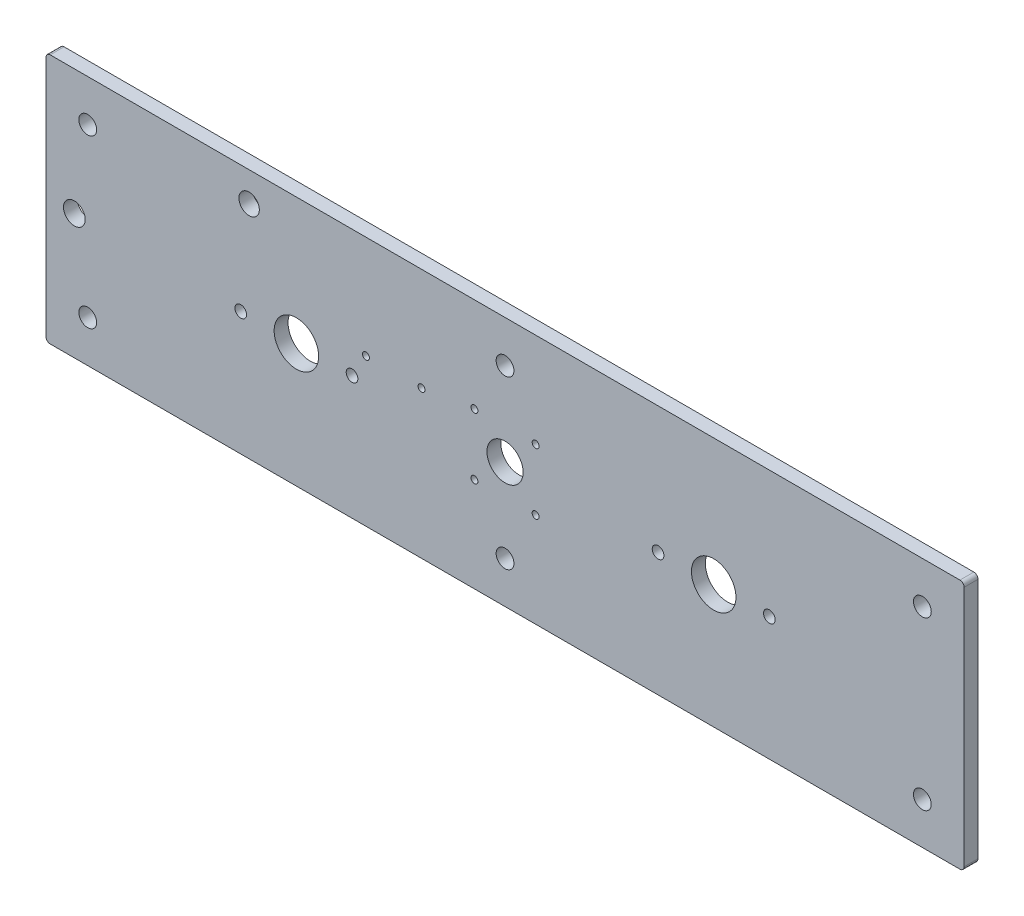
SolidWorks part; units mm, degrees
ref_plane "Front Plane" through (0, 0, 0) normal (0, 0, 1) x (1, 0, 0)
ref_plane "Top Plane" through (0, 0, 0) normal (0, 1, 0) x (1, 0, 0)
ref_plane "Right Plane" through (0, 0, 0) normal (1, 0, 0) x (0, 0, -1)
sketch "Sketch1" plane through (0, 0, 0) normal (0, 0, 1) x (1, 0, 0)
  line L1 (-165, -45) -> (165, -45)
  line L2 (-165, -45) -> (-165, 45)
  line L3 (-165, 45) -> (165, 45)
  line L4 (165, -45) -> (165, 45)
  line L5 (-165, -45) -> (165, 45) construction
  line L6 (-165, 45) -> (165, -45) construction
  point P0 (0, 0)
  dimension "D1" = 330
  dimension "D2" = 90
extrude "Boss-Extrude1" add sketch "Sketch1" along normal mid plane 5
hole_wizard "M6 Clearance Hole1" positions "Sketch6" profile "Sketch5" hole size "M6" standard "ANSI Metric"
sketch "Sketch6" plane through (0, 0, 2.5) normal (0, 0, 1) x (1, 0, 0)
  line L0 (-999.1588, 30) -> (49000.8412, 30) construction
  line L1 (-996.5045, -30) -> (49003.4955, -30) construction
  line L2 (-150, -995.3212) -> (-150, 49004.6788) construction
  line L3 (0, -1000) -> (0, 49000) construction
  line L4 (150, -1006.2702) -> (150, 48993.7298) construction
  line L5 (-165, 45) -> (-165, -45) construction
  line L6 (165, -45) -> (165, 45) construction
  line L7 (165, 45) -> (-165, 45) construction
  line L8 (-165, -45) -> (165, -45) construction
  point P27 (-150, 30)
  point P29 (-150, -30)
  point P31 (0, 30)
  point P33 (0, -30)
  point P35 (150, -30)
  point P37 (150, 30)
  dimension "D1" = 15
  dimension "D2" = 15
  dimension "D3" = 15
  dimension "D4" = 15
sketch "Sketch5" plane through (-150, 30, 2.5) normal (1, 0, 0) x (0, -1, 0)
  line L0 (0, 0) -> (0, 11.9228)
  line L1 (0, 11.9228) -> (3.2, 10)
  line L2 (3.2, 10) -> (3.2, 0)
  line L5 (3.2, 0) -> (0, 0)
  line L10 (0, 11.9228) -> (-3.2, 10) construction
  line L11 (0, -6.35) -> (0, 107.95) construction
  dimension "Hole Dia." = 6.4
  dimension "Hole Depth" = 10
  dimension "Drill Angle" = 118
sketch "Sketch3" plane through (0, 0, 2.5) normal (0, 0, 1) x (1, 0, 0)
  line L0 (-165, -0.6) -> (165, -0.6) construction
  circle A0 centre (-75, -0.6) radius 8
  dimension "D1" = 16
  dimension "D7" = 75
  dimension "D3" = 0.6
extrude "Cut-Extrude2" cut sketch "Sketch3" against normal through all
hole_wizard "M5x0.8 Tapped Hole1" positions "Sketch8" profile "Sketch7" tap size "M5x0.8" standard "ANSI Metric" end condition through all
sketch "Sketch8" plane through (0, 0, 2.5) normal (0, 0, 1) x (1, 0, 0)
  line L0 (-1080, -0.6) -> (48920, -0.6) construction
  circle A0 centre (-75, -0.6) radius 8 construction
  point P6 (-95, -0.6)
  point P8 (-55, -0.6)
  dimension "D1" = 20
  dimension "D2" = 20
sketch "Sketch7" plane through (-95, -0.6, 2.5) normal (1, 0, 0) x (0, -1, 0)
  line L0 (0, 0) -> (0, 5)
  line L1 (0, 5) -> (2.1, 5)
  line L2 (2.1, 5) -> (2.1, 0)
  line L5 (2.1, 0) -> (0, 0)
  line L11 (0, -6.35) -> (0, 107.95) construction
  dimension "Thru Tap Drill Dia." = 4.2
  dimension "Thru Tap Drill Depth" = 5
cosmetic thread "Hole Thread1" parameters "D2"=5
cosmetic thread "Hole Thread2" parameters "D2"=5
mirror "Mirror1" about plane through (0, 0, 0) normal (1, 0, 0) of "M5x0.8 Tapped Hole1", "Cut-Extrude2"
sketch "Sketch4" plane through (0, 0, 2.5) normal (0, 0, 1) x (1, 0, 0)
  circle A0 centre (0, 0) radius 6.5
  dimension "D1" = 13
extrude "Cut-Extrude3" cut sketch "Sketch4" against normal through all
hole_wizard "M3x0.5 Tapped Hole1" positions "Sketch10" profile "Sketch9" tap size "M3x0.5" standard "ANSI Metric" end condition through all
sketch "Sketch10" plane through (0, 0, 2.5) normal (0, 0, 1) x (1, 0, 0)
  line L1 (-11, -11) -> (11, -11) construction
  line L2 (-11, -11) -> (-11, 11) construction
  line L3 (-11, 11) -> (11, 11) construction
  line L4 (11, -11) -> (11, 11) construction
  line L5 (-11, -11) -> (11, 11) construction
  line L6 (-11, 11) -> (11, -11) construction
  point P2 (11, 11)
  point P67 (-11, -11)
  point P68 (-11, 11)
  point P69 (11, -11)
  dimension "D1" = 22
  dimension "D2" = 22
  dimension "D3" = 11
  dimension "D4" = 11
sketch "Sketch9" plane through (11, 11, 2.5) normal (1, 0, 0) x (0, -1, 0)
  line L0 (0, 0) -> (0, 5)
  line L1 (0, 5) -> (1.25, 5)
  line L2 (1.25, 5) -> (1.25, 0)
  line L5 (1.25, 0) -> (0, 0)
  line L11 (0, -6.35) -> (0, 107.95) construction
  dimension "Thru Tap Drill Dia." = 2.5
  dimension "Thru Tap Drill Depth" = 5
cosmetic thread "Hole Thread3" parameters "D2"=3
cosmetic thread "Hole Thread4" parameters "D2"=3
cosmetic thread "Hole Thread5" parameters "D2"=3
cosmetic thread "Hole Thread6" parameters "D2"=3
fillet "Fillet1" radius 1.5 4 edges at (-165, -45, 0) (-165, 45, 0) (165, -45, 0) (165, 45, 0)
hole_wizard "M3x0.5 Tapped Hole2" positions "Sketch12" profile "Sketch11" tap size "M3x0.5" standard "ANSI Metric" end condition through all
sketch "Sketch12" plane through (0, 0, 2.5) normal (0, 0, 1) x (1, 0, 0)
  line L0 (-50, 8) -> (-30, 8) construction
  point P0 (-30, 8)
  point P2 (-50, 8)
  dimension "D1" = 20
  dimension "D2" = 30
  dimension "D3" = 8
sketch "Sketch11" plane through (-30, 8, 2.5) normal (1, 0, 0) x (0, -1, 0)
  line L0 (0, 0) -> (0, 5)
  line L1 (0, 5) -> (1.25, 5)
  line L2 (1.25, 5) -> (1.25, 0)
  line L5 (1.25, 0) -> (0, 0)
  line L11 (0, -6.35) -> (0, 107.95) construction
  dimension "Thru Tap Drill Dia." = 2.5
  dimension "Thru Tap Drill Depth" = 5
cosmetic thread "Hole Thread7" parameters "D2"=3
cosmetic thread "Hole Thread8" parameters "D2"=3
sketch "Sketch13" plane through (0, 0, 2.5) normal (0, 0, 1) x (1, 0, 0)
  circle A0 centre (-91.9931, 34.3559) radius 3.6711
extrude "Cut-Extrude4" cut sketch "Sketch13" against normal through all
sketch "Sketch14" plane through (0, 0, 2.5) normal (0, 0, 1) x (1, 0, 0)
  circle A0 centre (-154.806, 0) radius 3.9072
extrude "Cut-Extrude5" cut sketch "Sketch14" against normal blind 10
